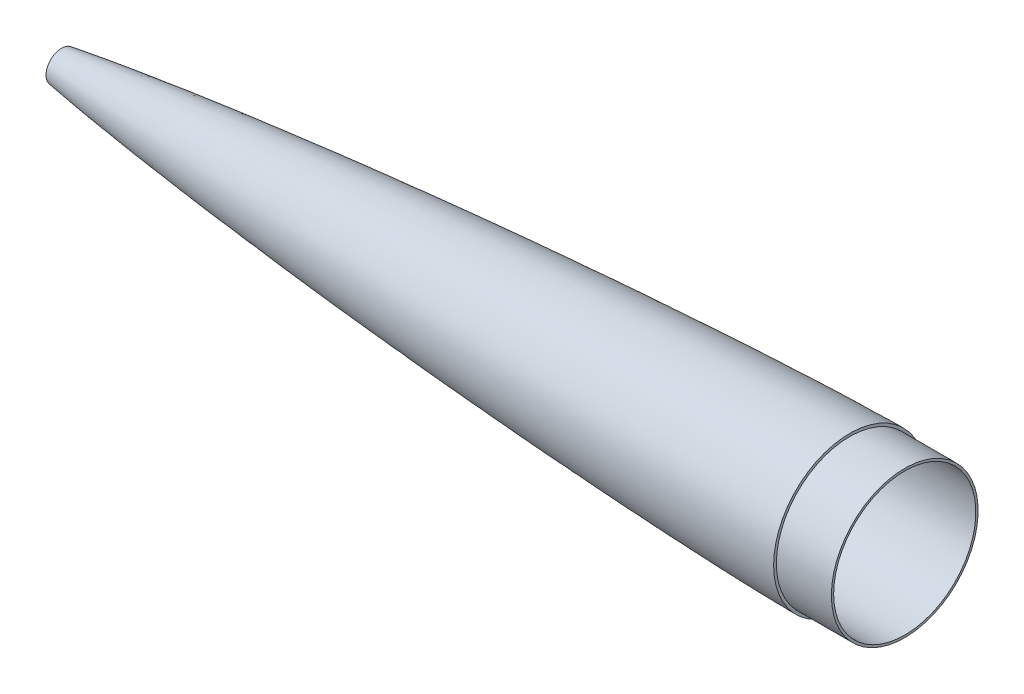
SolidWorks part; units mm, degrees
material "Hexcel AS4C (3000 Filaments)"
ref_plane "Front Plane" through (0, 0, 0) normal (0, 0, 1) x (1, 0, 0)
ref_plane "Top Plane" through (0, 0, 0) normal (0, 1, 0) x (1, 0, 0)
ref_plane "Right Plane" through (0, 0, 0) normal (1, 0, 0) x (0, 0, -1)
sketch "Sketch1" plane through (0, 0, 0) normal (0, 0, 1) x (1, 0, 0)
  line L0 (0, 0) -> (596.9, 0)
  line L2 (596.9, 0) -> (596.9, 52.7482)
  spline S0 degree 4 poles (0, 0) (0.0024, 0.0056) (0.008, 0.0163) (0.0233, 0.0353) (0.0583, 0.069) (0.1105, 0.1106) (0.1804, 0.1587) (0.2798, 0.2202) (0.3991, 0.287) (0.5391, 0.3592) (0.6997, 0.4363) (0.9322, 0.5415) (1.293, 0.6933) (1.9132, 0.9318) (3.0286, 1.3168) (5.0297, 1.9288) (8.7193, 2.9162) (15.6155, 4.5123) (27.7821, 6.9272) (48.0381, 10.379) (75.5616, 14.4184) (108.703, 18.7111) (145.1674, 22.9502) (181.6719, 26.826) (218.2071, 30.3992) (254.767, 33.7085) (291.348, 36.7768) (327.9472, 39.6184) (364.5629, 42.24) (401.1936, 44.6421) (437.8384, 46.8187) (474.4967, 48.7564) (506.5841, 50.2205) (534.0958, 51.2823) (556.2771, 51.9856) (571.2063, 52.3703) (583.4683, 52.6116) (591.1434, 52.712) (594.9811, 52.744) (596.9, 52.7482) knots 0 0 0 0 0 0.00004 0.000081 0.000162 0.000323 0.000485 0.000646 0.00094 0.001234 0.001534 0.001834 0.002641 0.003843 0.005963 0.009698 0.016588 0.029299 0.05314 0.092371 0.153547 0.214723 0.275899 0.337075 0.398251 0.459427 0.520603 0.581779 0.642954 0.70413 0.765306 0.826482 0.887658 0.918246 0.948834 0.974417 0.987208 1 1 1 1 1 construction
  spline S1 degree 4 poles (0, 0) (0.0024, 0.0056) (0.008, 0.0163) (0.0233, 0.0353) (0.0583, 0.069) (0.1105, 0.1106) (0.1804, 0.1587) (0.2798, 0.2202) (0.3991, 0.287) (0.5391, 0.3592) (0.6997, 0.4363) (0.9322, 0.5415) (1.293, 0.6933) (1.9132, 0.9318) (3.0286, 1.3168) (5.0297, 1.9288) (8.7193, 2.9162) (15.6155, 4.5123) (27.7821, 6.9272) (48.0381, 10.379) (75.5616, 14.4184) (108.703, 18.7111) (145.1674, 22.9502) (181.6719, 26.826) (218.2071, 30.3992) (254.767, 33.7085) (291.348, 36.7768) (327.9472, 39.6184) (364.5629, 42.24) (401.1936, 44.6421) (437.8384, 46.8187) (474.4967, 48.7564) (506.5841, 50.2205) (534.0958, 51.2823) (556.2771, 51.9856) (571.2063, 52.3703) (583.4683, 52.6116) (591.1434, 52.712) (594.9811, 52.744) (596.9, 52.7482) knots 0 0 0 0 0 0.00004 0.000081 0.000162 0.000323 0.000485 0.000646 0.00094 0.001234 0.001534 0.001834 0.002641 0.003843 0.005963 0.009698 0.016588 0.029299 0.05314 0.092371 0.153547 0.214723 0.275899 0.337075 0.398251 0.459427 0.520603 0.581779 0.642954 0.70413 0.765306 0.826482 0.887658 0.918246 0.948834 0.974417 0.987208 1 1 1 1 1
  dimension "D1" = 596.9
revolve "Revolve1" add sketch "Sketch1" angle 360 about L0
shell "Shell1" thickness 1.9101 removed face at (596.9, 0, 52.7482)
ref_plane "Shoulder Plane" through (558.8, 0, 0) normal (1, 0, 0) x (0, 0, -1)
sketch "Sketch2" plane through (558.8, 0, 0) normal (1, 0, 0) x (0, 0, -1)
  circle A0 centre (0, 0) radius 49.2506
  circle A1 centre (0, 0) radius 50.8381
  circle A2 centre (0, 0) radius 50.8381
  dimension "D2" = 1.5875
  dimension "D1" = 0
extrude "Boss-Extrude1" add sketch "Sketch2" along normal blind 76.2
ref_plane "Tip Cut Plane" through (50.8, 0, 0) normal (1, 0, 0) x (0, 0, -1)
sketch "Sketch3" plane through (50.8, 0, 0) normal (1, 0, 0) x (0, 0, -1)
  circle A0 centre (0, 0) radius 38.1
  dimension "D1" = 76.2
extrude "Cut-Extrude1" cut sketch "Sketch3" against normal blind 50.8
